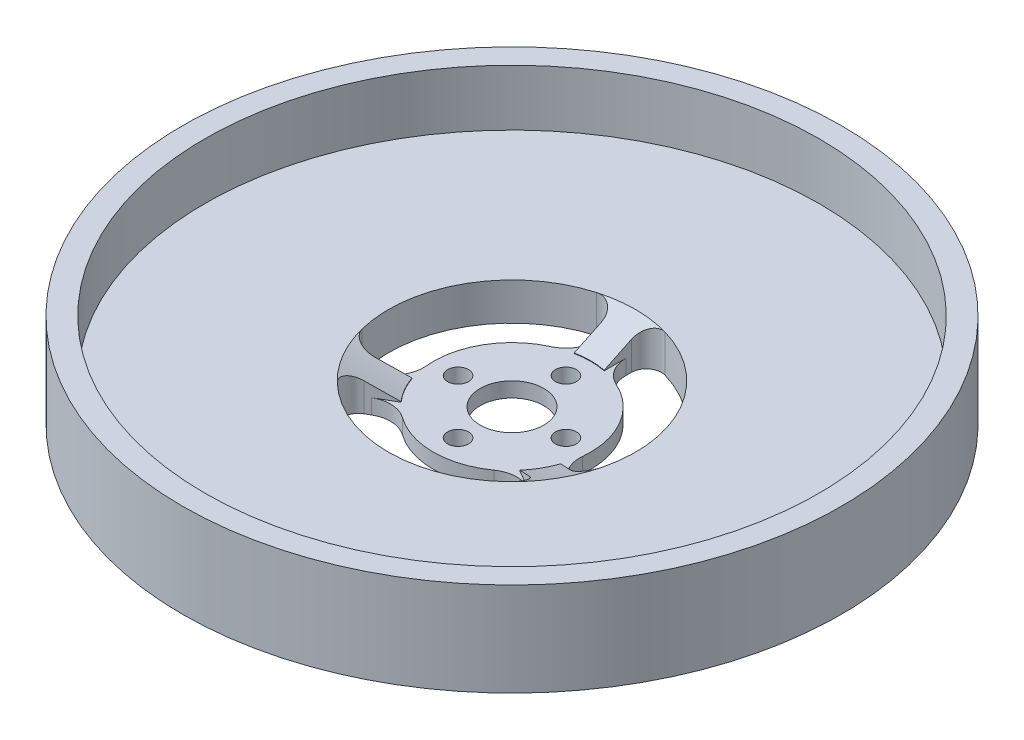
SolidWorks part; units mm, degrees
ref_plane "Front Plane" through (0, 0, 0) normal (0, 0, 1) x (1, 0, 0)
ref_plane "Top Plane" through (0, 0, 0) normal (0, 1, 0) x (1, 0, 0)
ref_plane "Right Plane" through (0, 0, 0) normal (1, 0, 0) x (0, 0, -1)
sketch "Sketch2" plane through (0, 0, 0) normal (0, 1, 0) x (1, 0, 0)
  circle A0 centre (0, 0) radius 44
extrude "Boss-Extrude2" add sketch "Sketch2" along normal blind 12.5
sketch "Sketch5" plane through (0, 12.5, 0) normal (0, 1, 0) x (1, 0, 0)
  circle A0 centre (0, 0) radius 41
  dimension "D1" = 82
extrude "Cut-Extrude2" cut sketch "Sketch5" against normal blind 7.5
sketch "Sketch6" plane through (0, 5, 0) normal (0, 1, 0) x (1, 0, 0)
  circle A0 centre (0, 0) radius 10.5
extrude "Cut-Extrude3" cut sketch "Sketch6" against normal blind 3
sketch "Sketch7" plane through (0, 2, 0) normal (0, 1, 0) x (1, 0, 0)
  circle A0 centre (0, 0) radius 4.25
  dimension "D1" = 8.5
extrude "Cut-Extrude4" cut sketch "Sketch7" against normal through all
sketch "Sketch8" plane through (0, 2, 0) normal (0, 1, 0) x (1, 0, 0)
  line L0 (-32.1696, 7.2) -> (36.5413, 7.2) construction
  circle A0 centre (0, 7.2) radius 1.4
  dimension "D1" = 7.2
extrude "Cut-Extrude5" cut sketch "Sketch8" against normal through all
pattern_circular "CirPattern2" count 4 over 360 about axis through (0, 2, 0) along (0, 1, 0) of "Cut-Extrude5"
sketch "Sketch11" plane through (0, 0, 0) normal (0, -1, 0) x (1, 0, 0)
  line L0 (0, 0) -> (0, -24.4942) construction
  line L1 (0, 0) -> (40.7412, 23.522) construction
  line L2 (-2, -10.3078) -> (-2, -16.3783)
  line L3 (0, 0) -> (-45.2396, 26.1191) construction
  line L4 (2, -10.3078) -> (2, -16.3783)
  line L5 (15.1841, 6.4571) -> (9.9268, 3.4218)
  line L6 (13.1841, 9.9212) -> (7.9268, 6.8859)
  line L7 (-7.9268, 6.8859) -> (-13.1841, 9.9212)
  line L8 (-15.1841, 6.4571) -> (-9.9268, 3.4218)
  circle A0 centre (0, 0) radius 10.5
  circle A1 centre (0, 0) radius 16.5
  dimension "D1" = 6
  dimension "D2" = 21
  dimension "D3" = 2
  dimension "D4" = 4
  dimension "D5" = 120
  dimension "D6" = 120
  dimension "D7" = 2
  dimension "D8" = 2
  dimension "D9" = 2
  dimension "D10" = 2
extrude "Cut-Extrude6" cut sketch "Sketch11" against normal blind 9 contours L6 A1 L7 A0 | L8 A1 L2 A0 | L4 A1 L5 A0 region at (-10.3663, 0, -5.985) region at (10.3663, 0, -5.985) region at (0, 0, 11.97)
chamfer "Chamfer1" distance 6 angle 26 3 edges at (-9.0933, 5, 5.25) (0, 5, -10.5) (9.0933, 5, 5.25) first distance on face at (0, 5, 41)
fillet "Fillet2" radius 4 6 edges at (7.9268, 1, 6.8859) (9.9268, 1, 3.4218) (2, 1, -10.3078) (-2, 1, -10.3078) (-9.9268, 1, 3.4218) (-7.9268, 1, 6.8859)
fillet "Fillet3" radius 2 6 edges at (15.1841, 2.5, 6.4571) (13.1841, 2.5, 9.9212) (-15.1841, 2.5, 6.4571) (-13.1841, 2.5, 9.9212) (2, 2.5, -16.3783) (-2, 2.5, -16.3783)
